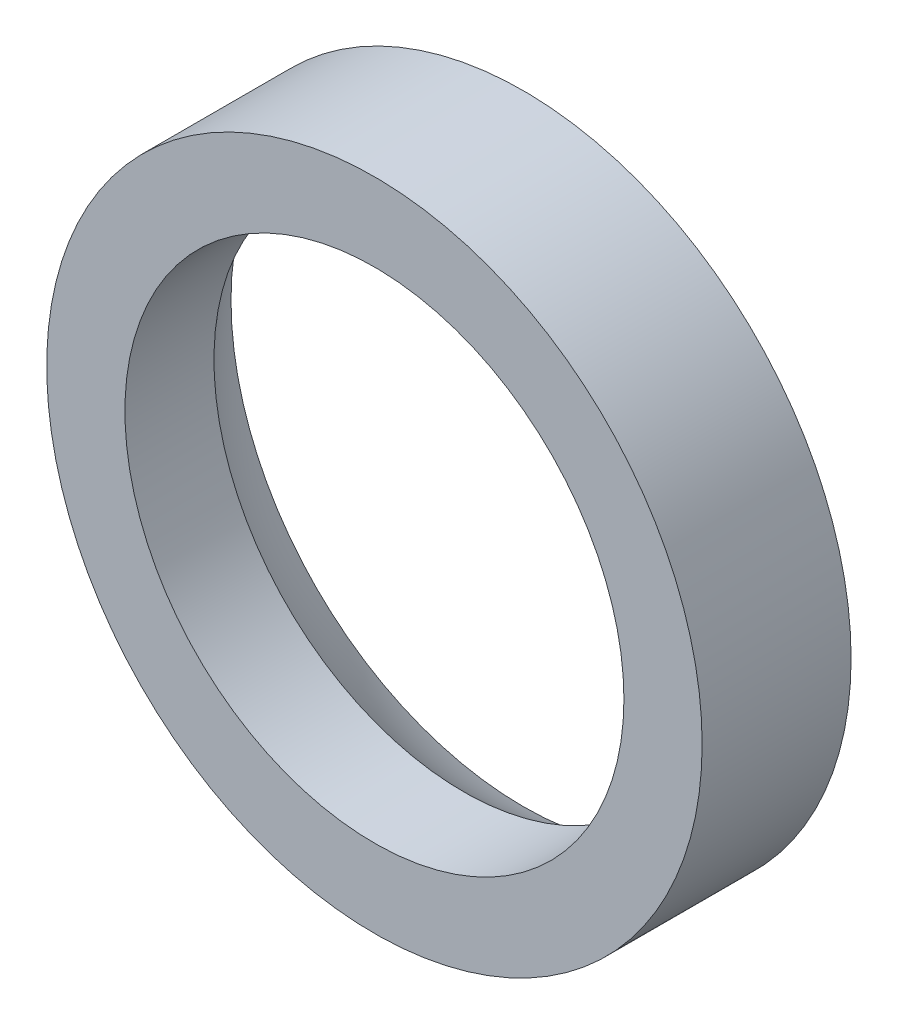
SolidWorks part; units mm, degrees
ref_plane "Ebene vorne" through (0, 0, 0) normal (0, 0, 1) x (1, 0, 0)
ref_plane "Ebene oben" through (0, 0, 0) normal (0, 1, 0) x (1, 0, 0)
ref_plane "Ebene rechts" through (0, 0, 0) normal (1, 0, 0) x (0, 0, -1)
sketch "Skizze1" plane through (0, 0, 0) normal (1, 0, 0) x (0, 0, -1)
  line L0 (-2, 4.4) -> (-2, 3.35)
  line L1 (-2, 3.35) -> (-0.8046, 3.35)
  line L2 (0, 3.9256) -> (0, 4.4)
  line L3 (0, 4.4) -> (-2, 4.4)
  line L4 (0, 0) -> (-2, 0) construction
  arc A0 (-0.8046, 3.35) -> (0, 3.9256) centre (2.2, 0) cw
revolve "Rotation1" add sketch "Skizze1" angle 360 about L4 reverse direction yes
ref_plane "Ebene1" through (0, 0, 2) normal (0, 0, 1) x (1, 0, 0)
ref_plane "kugel XY" through (0, 0, 2) normal (0, 0, 1) x (1, 0, 0)
ref_plane "kugel XZ" through (0, 0, 0) normal (0, -1, 0) x (-1, 0, 0)
ref_plane "kugel YZ" through (0, 0, 0) normal (1, 0, 0) x (0, 0, -1)
ref_axis "kugel X" through (-80.9, 0, 2) along (1, 0, 0)
ref_axis "kugel Y" through (0, -50, 2) along (0, 1, 0)
ref_axis "kugel Z" through (0, 0, 80.9) along (0, 0, -1)
sketch3d "kugel"
  point P0 (0, 0, 2)
